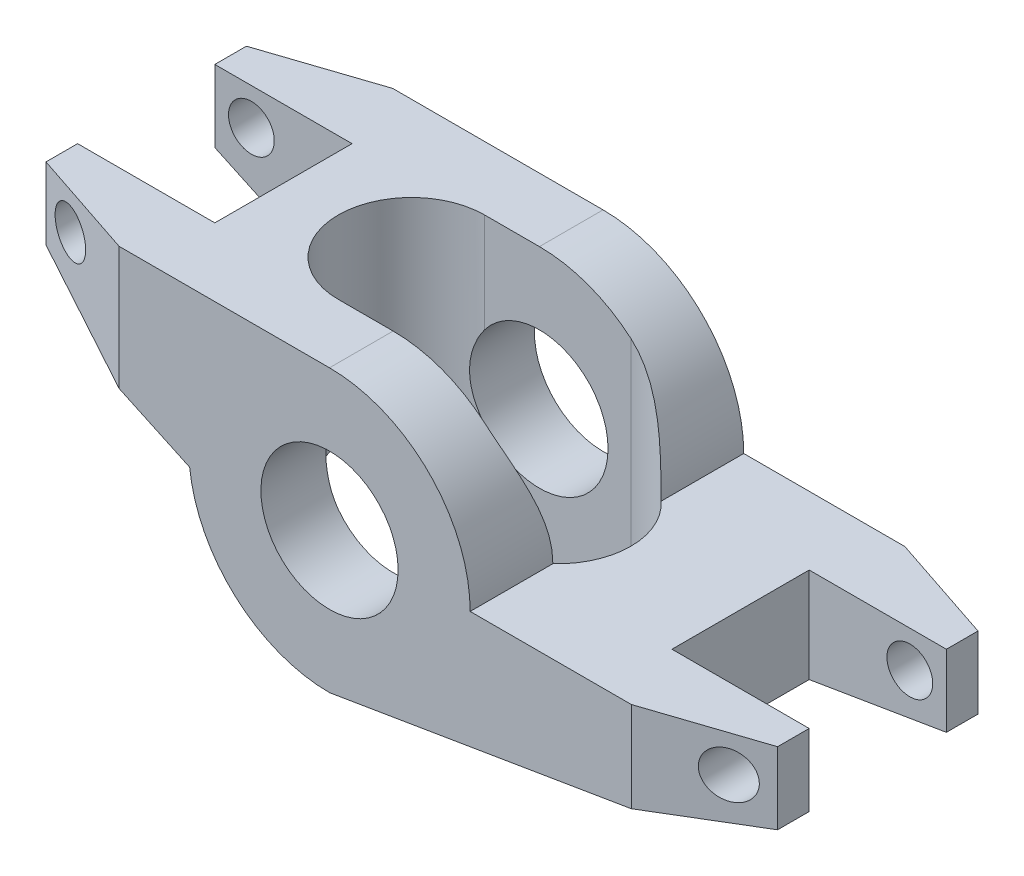
SolidWorks part; units mm, degrees
ref_plane "Front Plane" through (0, 0, 0) normal (0, 0, 1) x (1, 0, 0)
ref_plane "Top Plane" through (0, 0, 0) normal (0, 1, 0) x (1, 0, 0)
ref_plane "Right Plane" through (0, 0, 0) normal (1, 0, 0) x (0, 0, -1)
sketch "Sketch1" plane through (0, 0, 0) normal (0, 0, 1) x (1, 0, 0)
  line L0 (0, 0) -> (0, -5)
  line L1 (0, -5) -> (12.5185, -10.8375)
  line L2 (0, 0) -> (22.23, 0)
  line L3 (22.23, -19.54) -> (50.81, -14.77)
  line L4 (50.81, -14.77) -> (50.81, -9.77)
  line L5 (50.81, -9.77) -> (32, -9.77)
  arc A0 (12.5185, -10.8375) -> (22.23, -19.54) centre (22.23, -9.77) ccw
  arc A1 (32, -9.77) -> (22.23, 0) centre (22.23, -9.77) ccw
  circle A2 centre (22.23, -9.77) radius 4.765
  circle A3 centre (2.54, -2.54) radius 1.59
  circle A4 centre (48.27, -12.31) radius 1.59
  dimension "D3" = 19.54
  dimension "D7" = 9.53
  dimension "D8" = 3.18
  dimension "D11" = 3.18
  dimension "D12" = 2.54
  dimension "D13" = 2.54
  dimension "D1" = 25
  dimension "D2" = 22.23
  dimension "D4" = 5
  dimension "D5" = 28.58
  dimension "D6" = 5
  dimension "D9" = 2.54
  dimension "D10" = 2.54
extrude "Boss-Extrude1" add sketch "Sketch1" along normal mid plane 19
chamfer "Chamfer1" distance 2.54 distance2 7.62 3 edges at (50.81, -12.27, 9.5) (0, -2.5, -9.5) (0, -2.5, 9.5) first distance on face at (50.81, -12.27, 0) first distance on face at (0, -2.5, 0)
chamfer "Chamfer2" distance 7.62 distance2 2.54 1 edges at (50.81, -12.27, -9.5) first distance on face at (25.7747, -9.1343, -9.5)
sketch "Sketch2" plane through (0, 0, 0) normal (0, 1, 0) x (1, 0, 0)
  line L0 (0, -6.96) -> (0, 6.96) construction
  line L1 (0, 4.765) -> (9.53, 4.765)
  line L2 (0, 4.765) -> (0, -4.765)
  line L3 (0, -4.765) -> (9.53, -4.765)
  line L4 (9.53, 4.765) -> (9.53, -4.765)
  line L5 (50.81, -6.96) -> (50.81, 6.96) construction
  line L6 (50.81, 4.765) -> (41.28, 4.765)
  line L7 (50.81, 4.765) -> (50.81, -4.765)
  line L8 (50.81, -4.765) -> (41.28, -4.765)
  line L9 (41.28, 4.765) -> (41.28, -4.765)
  line L10 (22.23, -9.5) -> (22.23, 9.5) construction
  line L11 (0, 0) -> (22.23, 0) construction
  point P18 (9.53, 0)
  point P19 (41.28, 0)
  dimension "D1" = 9.53
  dimension "D2" = 9.53
  dimension "D3" = 9.53
  dimension "D4" = 9.53
extrude "Cut-Extrude1" cut sketch "Sketch2" against normal through all
sketch "Sketch3" plane through (0, 0, 0) normal (0, 1, 0) x (1, 0, 0)
  line L0 (9.53, 0) -> (23.5, 0) construction
  line L1 (9.53, -4.765) -> (9.53, 4.765) construction
  line L2 (41.28, -4.765) -> (41.28, 4.765) construction
  line L3 (18.42, 5.08) -> (28.58, 5.08)
  line L4 (18.42, -5.08) -> (28.58, -5.08)
  line L5 (33.66, 0) -> (41.28, 0) construction
  arc A0 (18.42, 5.08) -> (18.42, -5.08) centre (18.42, 0) ccw
  arc A1 (28.58, -5.08) -> (28.58, 5.08) centre (28.58, 0) ccw
  dimension "D1" = 10.16
  dimension "D3" = 10.16
  dimension "D2" = 8.89
extrude "Cut-Extrude2" cut sketch "Sketch3" against normal through all
